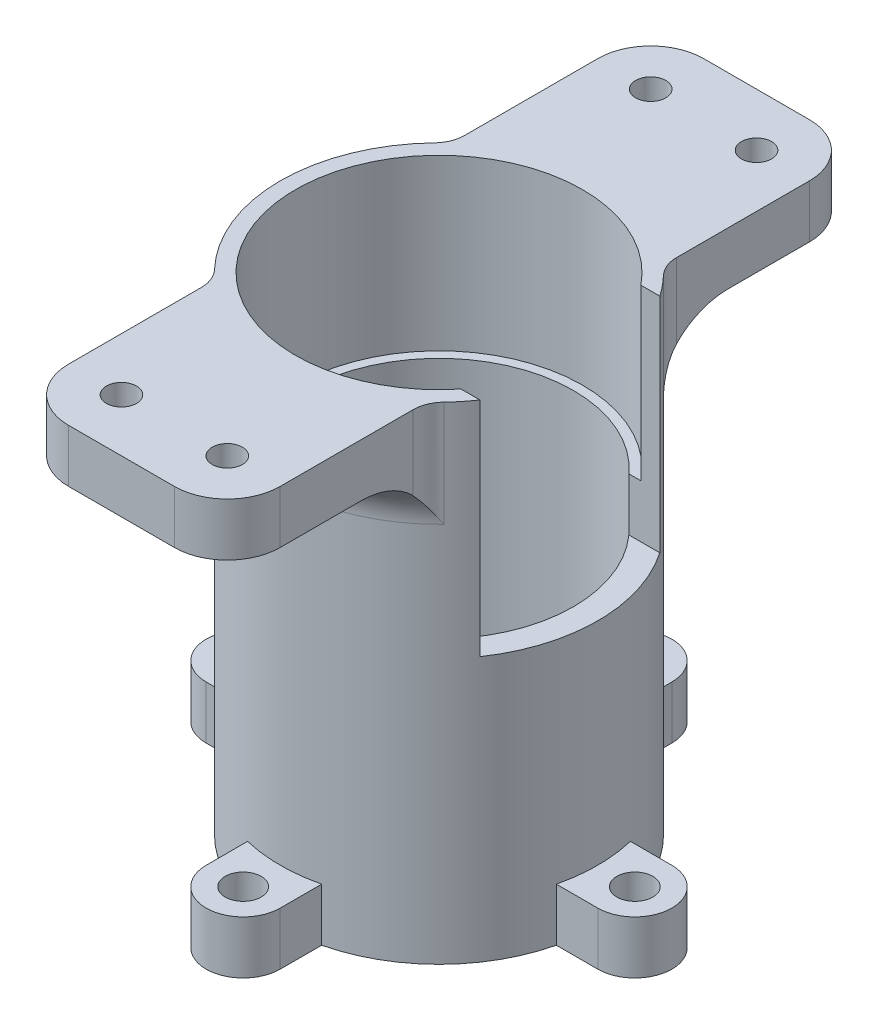
SolidWorks part; units mm, degrees
material "ABS"
ref_plane "前视基准面" through (0, 0, 0) normal (0, 0, 1) x (1, 0, 0)
ref_plane "上视基准面" through (0, 0, 0) normal (0, 1, 0) x (1, 0, 0)
ref_plane "右视基准面" through (0, 0, 0) normal (1, 0, 0) x (0, 0, -1)
sketch "草图1" plane through (0, 0, 0) normal (0, 1, 0) x (1, 0, 0)
  circle A0 centre (0, 0) radius 15
  circle A1 centre (0, 0) radius 12.7
  dimension "D1" = 30
  dimension "D2" = 25.4
extrude "凸台-拉伸1" add sketch "草图1" along normal blind 30
sketch "草图2" plane through (0, 0, 0) normal (0, 1, 0) x (1, 0, 0)
  line L0 (0, 0) -> (28.3565, 0) construction
  line L1 (18.5, 3.5) -> (14.586, 3.5)
  line L2 (18.5, -3.5) -> (14.586, -3.5)
  line L3 (3.5, -18.5) -> (3.5, -14.586)
  line L4 (-3.5, -18.5) -> (-3.5, -14.586)
  line L5 (-18.5, -3.5) -> (-14.586, -3.5)
  line L6 (-18.5, 3.5) -> (-14.586, 3.5)
  line L7 (-3.5, 18.5) -> (-3.5, 14.586)
  line L8 (3.5, 18.5) -> (3.5, 14.586)
  circle A0 centre (18.5, 0) radius 1
  arc A1 (18.5, -3.5) -> (18.5, 3.5) centre (18.5, 0) ccw
  circle A2 centre (0, 0) radius 15 construction
  circle A7 centre (0, 0) radius 15 construction
  arc A9 (18.5, 3.5) -> (15, 0) centre (18.5, 0) ccw construction
  arc A10 (15, 0) -> (18.5, -3.5) centre (18.5, 0) ccw construction
  arc A20 (14.586, 3.5) -> (14.586, -3.5) centre (0, 0) cw
  circle A21 centre (0, -18.5) radius 1
  arc A22 (-3.5, -18.5) -> (3.5, -18.5) centre (0, -18.5) ccw
  arc A23 (3.5, -14.586) -> (-3.5, -14.586) centre (0, 0) cw
  arc A24 (3.5, -18.5) -> (0, -15) centre (0, -18.5) ccw construction
  arc A25 (0, -15) -> (-3.5, -18.5) centre (0, -18.5) ccw construction
  circle A26 centre (-18.5, 0) radius 1
  arc A27 (-18.5, 3.5) -> (-18.5, -3.5) centre (-18.5, 0) ccw
  arc A28 (-14.586, -3.5) -> (-14.586, 3.5) centre (0, 0) cw
  arc A29 (-18.5, -3.5) -> (-15, 0) centre (-18.5, 0) ccw construction
  arc A30 (-15, 0) -> (-18.5, 3.5) centre (-18.5, 0) ccw construction
  circle A31 centre (0, 18.5) radius 1
  arc A32 (3.5, 18.5) -> (-3.5, 18.5) centre (0, 18.5) ccw
  arc A33 (-3.5, 14.586) -> (3.5, 14.586) centre (0, 0) cw
  arc A34 (-3.5, 18.5) -> (0, 15) centre (0, 18.5) ccw construction
  arc A35 (0, 15) -> (3.5, 18.5) centre (0, 18.5) ccw construction
  dimension "D1" = 7
  dimension "D2" = 2
  dimension "D4" = 4
  dimension "D3" = 15
extrude "凸台-拉伸2" add sketch "草图2" along normal blind 5
sketch "草图3" plane through (0, 30, 0) normal (0, 1, 0) x (1, 0, 0)
  line L0 (-25.3478, 0) -> (26.7359, 0) construction
  line L1 (0, 22.4604) -> (0, -23.8339) construction
  line L7 (9.0453, 8.4966) -> (20.9547, 8.4966)
  line L8 (9.0453, 8.4966) -> (9.0453, -8.4966)
  line L9 (9.0453, -8.4966) -> (20.9547, -8.4966)
  line L10 (20.9547, 8.4966) -> (20.9547, -8.4966)
  line L11 (15, -8.4966) -> (15, 8.4966) construction
  line L12 (9.0453, 0) -> (20.9547, 0) construction
  circle A1 centre (0, 0) radius 15 construction
  point P5 (15, 0)
extrude "切除-拉伸1" cut sketch "草图3" against normal blind 5
sketch "草图5" plane through (0, 5, 0) normal (0, 1, 0) x (1, 0, 0)
  circle A0 centre (0, -18.5) radius 1.7
  circle A1 centre (-18.5, 0) radius 1.7
  circle A2 centre (0, 18.5) radius 1.7
  circle A3 centre (18.5, 0) radius 1.7
  dimension "D1" = 3.4
  dimension "D2" = 4
extrude "切除-拉伸3" cut sketch "草图5" against normal blind 3
sketch "草图6" plane through (0, 30, 0) normal (0, 1, 0) x (1, 0, 0)
  line L0 (12.3616, 8.4966) -> (10.5736, 8.4966)
  line L1 (12.3616, -8.4966) -> (10.5736, -8.4966)
  arc A0 (12.3616, 8.4966) -> (12.3616, -8.4966) centre (0, 0) ccw
  arc A1 (10.5736, 8.4966) -> (10.5736, -8.4966) centre (0, 0) ccw
extrude "凸台-拉伸3" add sketch "草图6" along normal blind 16
sketch "草图7" plane through (0, 46, 0) normal (0, 1, 0) x (1, 0, 0)
  line L0 (0, 26.1418) -> (0, -30.3273) construction
  line L1 (-50.6464, 0) -> (48.1374, 0) construction
  line L2 (-10, -9.9973) -> (-10, -30)
  line L3 (-10, 30) -> (10, 30)
  line L4 (-10, 30) -> (-10, 9.9973)
  line L5 (-10, -30) -> (10, -30)
  line L6 (10, 30) -> (10, 9.9973)
  line L7 (0, -30) -> (0, 30) construction
  line L8 (-7.5, 0) -> (7.5, 0) construction
  line L9 (10, -9.9973) -> (10, -30)
  arc A0 (10, 9.9973) -> (-10, 9.9973) centre (0, 0) ccw
  arc A2 (-10, -9.9973) -> (10, -9.9973) centre (0, 0) ccw
  point P5 (0, 0)
  dimension "D1" = 20
  dimension "D2" = 60
extrude "凸台-拉伸4" add sketch "草图7" against normal blind 5
fillet "圆角1" radius 5 2 edges at (0, 41, -15) (0, 41, 15)
fillet "圆角4" radius 3 4 edges at (10, 41, 11.1803) (10, 41, -11.1803) (-10, 41, 11.1803) (-10, 41, -11.1803)
fillet "圆角6" radius 5 4 edges at (-10, 43.5, -30) (10, 43.5, -30) (10, 43.5, 30) (-10, 43.5, 30)
sketch "草图11" plane through (0, 46, 0) normal (0, 1, 0) x (1, 0, 0)
  line L0 (0, 33.1175) -> (0, -32.7209) construction
  line L1 (-32.1656, 0) -> (33.5935, 0) construction
  circle A0 centre (-5, 25) radius 1.425
  circle A1 centre (5, 25) radius 1.425
  circle A2 centre (5, -25) radius 1.425
  circle A3 centre (-5, -25) radius 1.425
  dimension "D1" = 2.85
extrude "切除-拉伸6" cut sketch "草图11" against normal blind 5
sketch "草图12" plane through (0, 41, 0) normal (0, -1, 0) x (1, 0, 0)
  line L0 (0, 30) -> (0, -30) construction
  line L1 (-5, 30) -> (5, 30) construction
  line L2 (5, -30) -> (-5, -30) construction
  line L3 (-22, 0) -> (22, 0) construction
  circle A0 centre (-5, -25) radius 1.95
  arc A1 (-18.5, 3.5) -> (-18.5, -3.5) centre (-18.5, 0) ccw construction
  arc A2 (18.5, -3.5) -> (18.5, 3.5) centre (18.5, 0) ccw construction
  circle A3 centre (5, -25) radius 1.95
  circle A4 centre (5, 25) radius 1.95
  circle A5 centre (-5, 25) radius 1.95
  dimension "D1" = 3.9
extrude "切除-拉伸7" cut sketch "草图12" against normal blind 3
